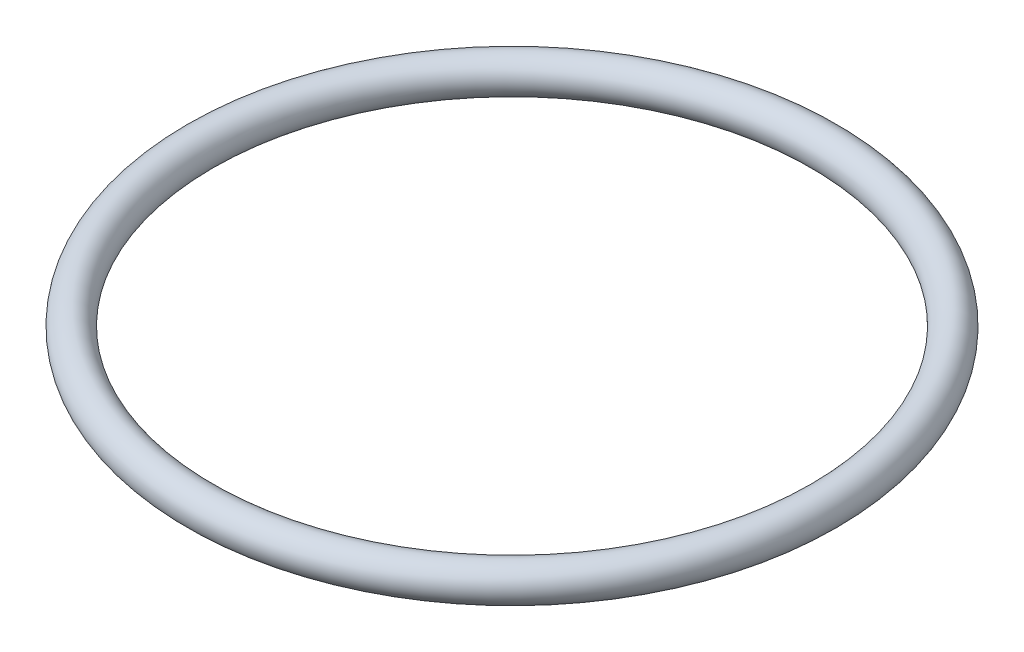
SolidWorks part; units mm, degrees
ref_plane "Front Plane" through (0, 0, 0) normal (0, 0, 1) x (1, 0, 0)
ref_plane "Top Plane" through (0, 0, 0) normal (0, 1, 0) x (1, 0, 0)
ref_plane "Right Plane" through (0, 0, 0) normal (1, 0, 0) x (0, 0, -1)
sketch "Sketch1" plane through (0, 0, 0) normal (0, 0, 1) x (1, 0, 0)
  circle A0 centre (0, 0) radius 2.667
  dimension "D1" = 5.334
sketch "Sketch2" plane through (0, 0, 0) normal (0, 1, 0) x (1, 0, 0)
  circle A0 centre (46.5455, 0) radius 46.5455
  dimension "D1" = 93.091
sweep "Sweep1" add profiles "Sketch1" path "Sketch2"
sketch "Sketch3" plane through (0, 0, 0) normal (0, 1, 0) x (1, 0, 0)
  point P0 (46.5455, 0)
ref_axis "Axis1" through (46.5455, 0, 0) along (0, 1, 0)
